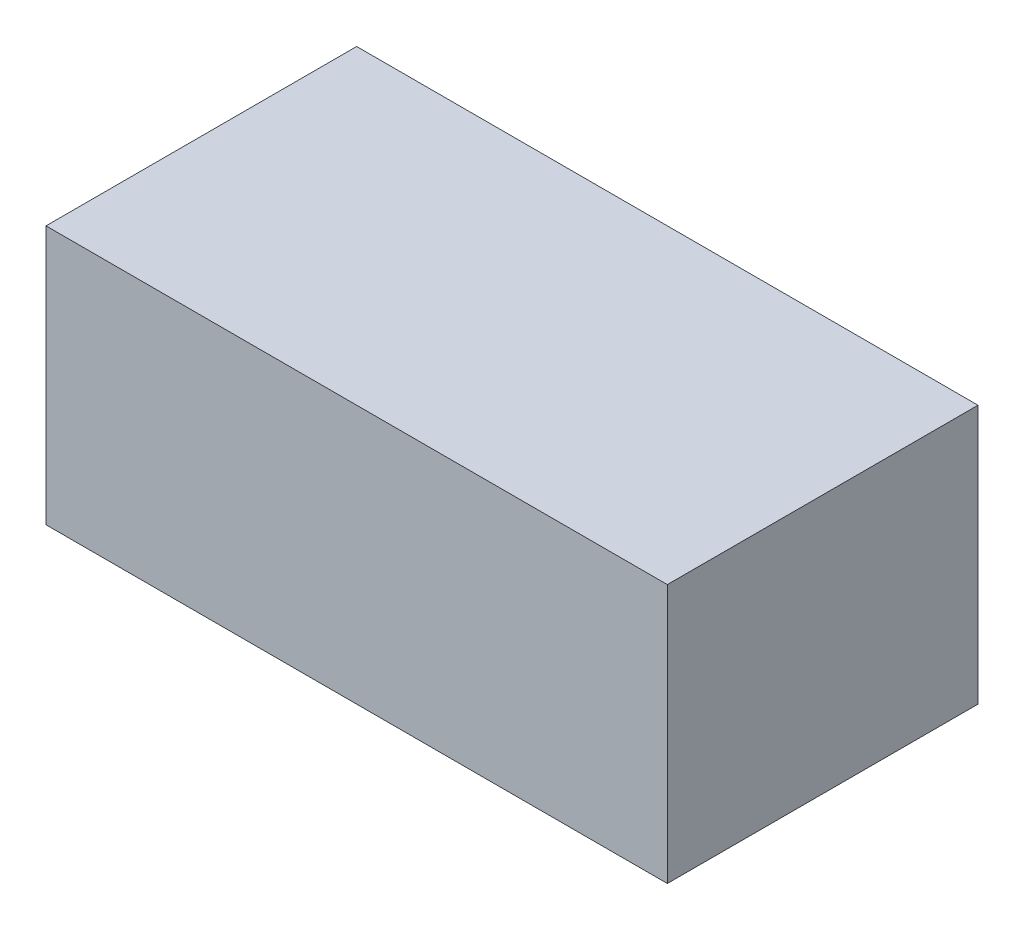
SolidWorks part; units mm, degrees
ref_plane "Front Plane" through (0, 0, 0) normal (0, 0, 1) x (1, 0, 0)
ref_plane "Top Plane" through (0, 0, 0) normal (0, 1, 0) x (1, 0, 0)
ref_plane "Right Plane" through (0, 0, 0) normal (1, 0, 0) x (0, 0, -1)
sketch "Sketch1" plane through (0, 0, 0) normal (1, 0, 0) x (0, 0, -1)
  line L1 (0, 0) -> (150, 0)
  line L2 (0, 0) -> (0, 125)
  line L3 (0, 125) -> (150, 125)
  line L4 (150, 0) -> (150, 125)
  dimension "D1" = 150
  dimension "D2" = 125
extrude "Boss-Extrude1" add sketch "Sketch1" along normal blind 300
equation "\"length\" = 300"
equation "\"height\"=150"
equation "\"D1@Sketch1\"=\"height\""
equation "\"width\"=125"
equation "\"D2@Sketch1\"=\"width\""
equation "\"D1@Boss-Extrude1\"=\"length\""
